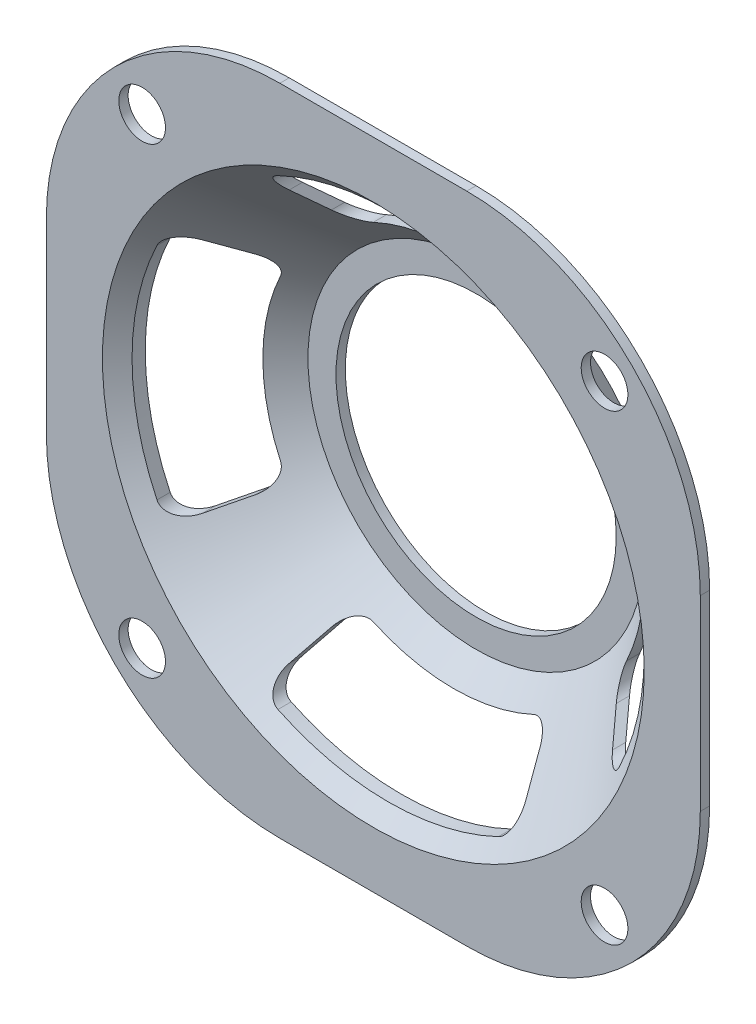
SolidWorks part; units mm, degrees
material "Cast Alloy Steel"
ref_plane "Front" through (0, 0, 0) normal (0, 0, 1) x (1, 0, 0)
ref_plane "Top" through (0, 0, 0) normal (0, 1, 0) x (1, 0, 0)
ref_plane "Right" through (0, 0, 0) normal (1, 0, 0) x (0, 0, -1)
sketch "Sketch1" plane through (0, 0, 0) normal (0, 0, 1) x (1, 0, 0)
  line L0 (35, -35) -> (-35, 35) construction
  line L1 (-10, -35) -> (10, -35)
  line L2 (-35, -10) -> (-35, 10)
  line L3 (-10, 35) -> (10, 35)
  line L4 (35, -10) -> (35, 10)
  arc A0 (-35, 10) -> (-10, 35) centre (-10, 10) cw
  arc A1 (10, 35) -> (35, 10) centre (10, 10) cw
  arc A2 (-10, -35) -> (-35, -10) centre (-10, -10) cw
  arc A3 (10, -35) -> (35, -10) centre (10, -10) ccw
  point P13 (-35, -35)
  dimension "D2" = 25
  dimension "D1" = 70
  dimension "D4" = 70
extrude "Extrude1" add sketch "Sketch1" against normal blind 1
ref_axis "Axis1" through (0, 0, 0.6) along (0, 0, -1)
sketch "Sketch6" plane through (0, 0, -1) normal (0, 0, -1) x (-1, 0, 0)
  circle A0 centre (0, 0) radius 30
  dimension "D1" = 60
extrude "Cut-Extrude1" cut sketch "Sketch6" against normal through all
sketch "Sketch7" plane through (0, 0, -1) normal (0, 0, -1) x (-1, 0, 0)
  line L0 (-24.7487, -24.7487) -> (24.7487, 24.7487) construction
  line L1 (-24.7487, 24.7487) -> (24.7487, -24.7487) construction
  circle A1 centre (-24.7487, 24.7487) radius 2.5
  circle A2 centre (24.7487, 24.7487) radius 2.5
  circle A3 centre (24.7487, -24.7487) radius 2.5
  circle A4 centre (-24.7487, -24.7487) radius 2.5
  arc A5 (-10, 35) -> (-35, 10) centre (-10, 10) ccw construction
  point P4 (-10, 10)
  dimension "D2" = 5
  dimension "D1" = 90
  dimension "D3" = 70
extrude "Cut-Extrude3" cut sketch "Sketch7" against normal through all
sketch "Sketch8" plane through (0, 0, 0) normal (1, 0, 0) x (0, 0, -1)
  line L0 (0, 30) -> (0, 29)
  line L5 (0, 29) -> (11, 18)
  line L6 (11, 18) -> (11, 15)
  line L7 (0, 0) -> (13.0042, 0) construction
  line L8 (1, 10) -> (1, 35) construction
  dimension "D1" = 3
  dimension "D2" = 1
  dimension "D3" = 135
  dimension "D4" = 10
revolve "Revolve-Thin1" add sketch "Sketch8" angle 360 about L7 wall 1
sketch "Sketch9" plane through (0, 0, -12) normal (0, 0, -1) x (-1, 0, 0)
  line L0 (11.1624, 19.3338) -> (12.6677, 21.9411)
  line L1 (-11.1624, 19.3338) -> (-12.6677, 21.9411)
  line L2 (0, 0) -> (0, 27.4142) construction
  arc A0 (-12.6677, 21.9411) -> (-11.7962, 24.7465) centre (-10.9356, 22.9411) cw
  arc A1 (-11.1624, 19.3338) -> (-8.5889, 18.5195) centre (-9.4304, 20.3338) ccw
  circle A2 centre (0, 0) radius 20.4142
  arc A3 (8.5889, 18.5195) -> (-8.5889, 18.5195) centre (0, 0) ccw
  arc A4 (12.6677, 21.9411) -> (11.7962, 24.7465) centre (10.9356, 22.9411) ccw
  arc A5 (11.1624, 19.3338) -> (8.5889, 18.5195) centre (9.4304, 20.3338) cw
  circle A6 centre (0, 0) radius 27.4142
  arc A7 (11.7962, 24.7465) -> (-11.7962, 24.7465) centre (0, 0) ccw
  dimension "D4" = 2
  dimension "D3" = 60
  dimension "D1" = 2
  dimension "D2" = 2
extrude "Cut-Extrude4" cut sketch "Sketch9" against normal through all
pattern_circular "CirPattern1" count 4 over 360 about axis through (0, 0, 0) along (0, 0, -1) of "Cut-Extrude4"
equation "\"D4@Sketch1\"=\"D1@Sketch1\""
equation "\"D3@Sketch7\" = \"D1@Sketch1\""
